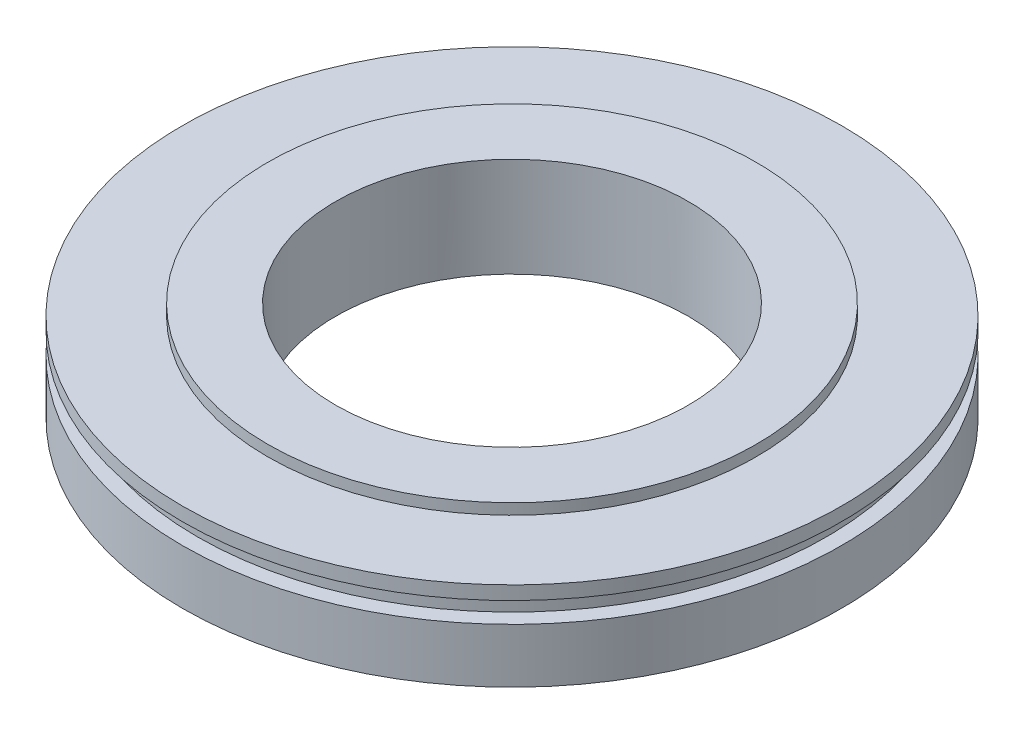
SolidWorks part; units mm, degrees
material "6061-T6 (SS)"
ref_plane "X-Y Datum" through (0, 0, 0) normal (0, 0, 1) x (1, 0, 0)
ref_plane "X-Z Datum" through (0, 0, 0) normal (0, 1, 0) x (1, 0, 0)
ref_plane "Y-Z Datum" through (0, 0, 0) normal (1, 0, 0) x (0, 0, -1)
sketch "Sketch1" plane through (0, 0, 0) normal (1, 0, 0) x (0, 0, -1)
  line L0 (-16.51, 2.6941) -> (-16.51, -5.0208)
  line L1 (-16.51, -5.0208) -> (-30.8407, -5.0208)
  line L4 (-29.4348, -0.5063) -> (-29.4348, 1.4241)
  line L7 (-30.8407, 2.6941) -> (-16.51, 2.6941)
  line L8 (0, 0) -> (0, -47872.0541) construction
  line L9 (0, 0) -> (-47872.0541, 0) construction
  line L10 (-30.8407, -0.5063) -> (-30.8407, -5.0208)
  line L11 (-14.7421, 2.6941) -> (15.0495, 2.6941) construction
  line L12 (-30.9994, 12.7) -> (-30.9994, -12.7) construction
  line L13 (14.2875, -5.0208) -> (-14.2875, -5.0208) construction
  line L15 (-30.8407, 2.6941) -> (-30.8407, 1.4241)
  line L16 (-30.8407, 1.4241) -> (-29.4348, 1.4241)
  line L17 (-29.4348, -0.5063) -> (-30.8407, -0.5063)
  point P15 (-30.9994, 0)
  dimension "D3" = 1.27
  dimension "D1" = 33.02
  dimension "D2" = 61.6814
  dimension "D4" = 1.9304
  dimension "D5" = 25.4
  dimension "D6" = 61.9989
  dimension "D7" = 1.5646
revolve "Revolve1" add sketch "Sketch1" angle 360 about L8
ref_plane "Plane1" through (0, 1.4241, 0) normal (0, 1, 0) x (1, 0, 0)
sketch "Sketch3" plane through (0, 2.6941, 0) normal (0, 1, 0) x (1, 0, 0)
  circle A0 centre (0, 0) radius 30.8407
  circle A1 centre (0, 0) radius 16.51
  circle A2 centre (0, 0) radius 16.51 construction
  circle A4 centre (0, 0) radius 30.8407 construction
extrude "BandAid Solution thicker" add sketch "Sketch3" along normal up to surface (-1.27 mm away) up to plane "Plane1"
sketch "Sketch4" plane through (0, 2.6941, 0) normal (0, 1, 0) x (1, 0, 0)
  circle A0 centre (0, 0) radius 16.51
  circle A1 centre (0, 0) radius 22.86
  circle A3 centre (0, 0) radius 16.51 construction
  dimension "D1" = 45.72
extrude "Lip for Bearing" add sketch "Sketch4" along normal blind 1.016
sketch "Sketch5" plane through (0, -5.0208, 0) normal (0, -1, 0) x (1, 0, 0)
  circle A3 centre (0, 0) radius 16.51
  circle A4 centre (0, 0) radius 30.8407
  circle A5 centre (0, 0) radius 30.8407 construction
  circle A6 centre (0, 0) radius 16.51 construction
extrude "Boss-Extrude1" add sketch "Sketch5" along normal blind 0.5791
